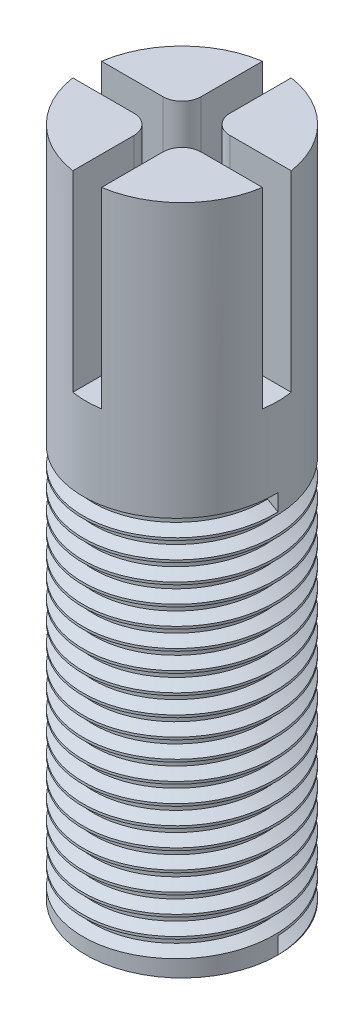
SolidWorks part; units mm, degrees
ref_plane "Alzado" through (0, 0, 0) normal (0, 0, 1) x (1, 0, 0)
ref_plane "Planta" through (0, 0, 0) normal (0, 1, 0) x (1, 0, 0)
ref_plane "Vista lateral" through (0, 0, 0) normal (1, 0, 0) x (0, 0, -1)
sketch "Croquis1" plane through (0, 0, 0) normal (0, 1, 0) x (1, 0, 0)
  circle A0 centre (0, 0) radius 5
  dimension "D1" = 10
extrude "Saliente-Extruir1" add sketch "Croquis1" along normal blind 35
sketch "Croquis2" plane through (0, 35, 0) normal (0, 1, 0) x (1, 0, 0)
  line L0 (0, 5) -> (0, 5.9579) construction
  line L1 (-5, 0) -> (-6.5506, 0) construction
  line L2 (0.75, 0.75) -> (5.9396, 0.75)
  line L3 (-0.75, -5.6789) -> (0.75, -5.6789)
  line L4 (-0.75, -5.6789) -> (-0.75, -0.75)
  line L5 (-0.75, 5.9579) -> (0.75, 5.9579)
  line L6 (0.75, -5.6789) -> (0.75, -0.75)
  line L9 (-6.5506, -0.75) -> (-0.75, -0.75)
  line L10 (-6.5506, -0.75) -> (-6.5506, 0.75)
  line L11 (-6.5506, 0.75) -> (-0.75, 0.75)
  line L12 (5.9396, -0.75) -> (5.9396, 0.75)
  line L15 (0.75, 0.75) -> (0.75, 5.9579)
  line L18 (4.9434, 0) -> (5, 0) construction
  line L20 (0, -5.6789) -> (0, -5) construction
  line L22 (-0.75, 0.75) -> (-0.75, 5.9579)
  line L27 (0.75, -0.75) -> (5.9396, -0.75)
  circle A0 centre (0, 0) radius 5 construction
  point P7 (0, 0)
  point P13 (0, 0)
  dimension "D1" = 1.5
  dimension "D2" = 1.5
  dimension "D3" = 0.75
  dimension "D4" = 0.75
  dimension "D5" = 12.4903
  dimension "D6" = 1.5
  dimension "D7" = 5.9579
  dimension "D8" = 5.9396
  dimension "D9" = 5.6789
extrude "Cortar-Extruir1" cut sketch "Croquis2" against normal blind 10
fillet "Redondeo1" radius 1 4 edges at (-0.75, 30, 0.75) (0.75, 30, 0.75) (0.75, 30, -0.75) (-0.75, 30, -0.75)
thread "Rosca1" pitch 1 method cut profile "Perfil de rosca1" start angle 0, offset 0, length 20, pitch 1, diameter 10
ref_plane "Plano1" through (5, 0, 0) normal (0, 0, 1) x (1, 0, 0)
sketch "Perfil de rosca1" plane through (5, 0, 0) normal (0, 0, 1) x (1, 0, 0)
  line L0 (0, 0) -> (0, 1) construction
  line L11 (0, 0) -> (0, 0.875)
  line L12 (0, 0.875) -> (-0.5413, 0.5625)
  line L13 (-0.5413, 0.5625) -> (-0.5413, 0.3125)
  line L15 (-0.5413, 0.3125) -> (0, 0)
  line L17 (-0.5413, 0.4375) -> (0, 0.4375) construction
  point P2 (0, 0)
  dimension "Pitch" = 1
  dimension "Profile_Angle" = 60
  dimension "Profile_Land" = 0.25
  dimension "Profile_Height" = 0.5413
